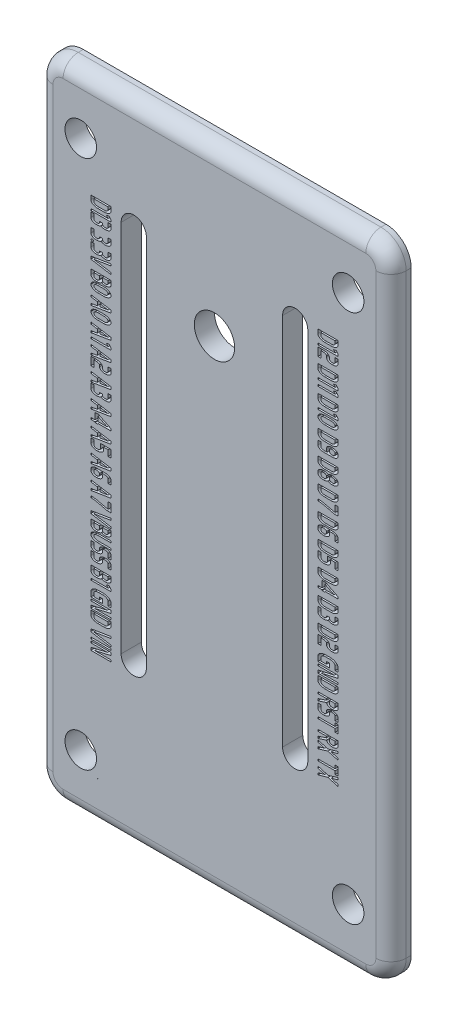
SolidWorks part; units mm, degrees
ref_plane "Front Plane" through (0, 0, 0) normal (0, 0, 1) x (1, 0, 0)
ref_plane "Top Plane" through (0, 0, 0) normal (0, 1, 0) x (1, 0, 0)
ref_plane "Right Plane" through (0, 0, 0) normal (1, 0, 0) x (0, 0, -1)
sketch "Sketch1" plane through (0, 0, 0) normal (0, 0, 1) x (1, 0, 0)
  line L1 (0, 32) -> (0, -32) construction
  line L2 (16.455, 32) -> (-16.455, 32) construction
  line L3 (-16.455, -32) -> (16.455, -32) construction
  line L4 (17.455, 31) -> (17.455, -31) construction
  line L5 (17.455, 0) -> (-17.455, 0) construction
  line L6 (-17.455, 31) -> (-17.455, -31) construction
  line L7 (17.7124, 32) -> (16.455, 32) construction
  line L8 (-15, -32) -> (15, -32)
  line L9 (-17.5, -29.5) -> (-17.5, 29.5)
  line L10 (-15, 32) -> (15, 32)
  line L11 (17.5, -29.5) -> (17.5, 29.5)
  line L12 (0, 32) -> (0, -32) construction
  line L13 (-17.5, 0) -> (17.5, 0) construction
  arc A0 (-15, -32) -> (-17.5, -29.5) centre (-15, -29.5) cw
  arc A1 (15, -32) -> (17.5, -29.5) centre (15, -29.5) ccw
  arc A2 (15, 32) -> (17.5, 29.5) centre (15, 29.5) cw
  arc A3 (-17.5, 29.5) -> (-15, 32) centre (-15, 29.5) cw
  circle A4 centre (-11.5563, -27.8796) radius 0.0197
  circle A5 centre (-13.25, -26.25) radius 1.5625
  circle A6 centre (-13.25, 26.25) radius 1.5625
  circle A7 centre (-13.25, -26.25) radius 2.37 construction
  circle A8 centre (13.25, -26.25) radius 1.5625
  circle A9 centre (13.25, 26.25) radius 1.5625
  point P12 (0, 0)
  point P25 (17.5, 32)
  dimension "D3" = 2.5
  dimension "D4" = 0.0393
  dimension "D5" = 3.125
  dimension "D1" = 35
  dimension "D2" = 64
  dimension "D6" = 11.5563
  dimension "D7" = 27.8796
extrude "Boss-Extrude1" add sketch "Sketch1" along normal blind 2
sketch "Sketch2" plane through (0, 0, 2) normal (0, 0, 1) x (1, 0, 0)
  line L0 (-13.6273, 22.1478) -> (-13.6273, -16.8522) construction
  line L1 (-11.75, 22.1478) -> (-15.5046, 22.1478) construction
  line L2 (-15.5046, -16.8522) -> (-11.75, -16.8522) construction
  line L4 (0, 2.52) -> (-13.6273, 2.52) construction
  line L6 (-8, -16) -> (-8, 21.04) construction
  line L9 (0, -16.85) -> (0, 21.89) construction
  line L12 (-9.25, -16) -> (-9.25, 21.04)
  line L15 (-6.75, -16) -> (-6.75, 21.04)
  line L16 (8, -16) -> (8, 21.04) construction
  line L17 (9.25, -16) -> (9.25, 21.04)
  line L18 (6.75, -16) -> (6.75, 21.04)
  line L19 (17.5, -29.5) -> (17.5, 29.5) construction
  line L20 (-15, -32) -> (15, -32) construction
  line L21 (-13.6273, 2.6478) -> (0, 2.6478) construction
  arc A4 (-9.25, -16) -> (-6.75, -16) centre (-8, -16) ccw
  arc A5 (-6.75, 21.04) -> (-9.25, 21.04) centre (-8, 21.04) ccw
  arc A6 (9.25, -16) -> (6.75, -16) centre (8, -16) cw
  arc A7 (6.75, 21.04) -> (9.25, 21.04) centre (8, 21.04) cw
  point P11 (8, 2.52)
  point P14 (-8, 2.52)
  dimension "D3" = 17.5
  dimension "D4" = 16
  dimension "D2" = 9.5
  dimension "D1" = 2.5
  dimension "D5" = 34.52
fillet "Fillet1" radius 1.5 8 edges at (-16.7678, -31.2678, 2) (0, -32, 2) (16.7678, -31.2678, 2) (16.7678, 31.2678, 2) (17.5, 0, 2) (-16.7678, 31.2678, 2) (-17.5, 0, 2) (0, 32, 2)
sketch "Sketch3" plane through (0, 0, 2) normal (0, 0, 1) x (1, 0, 0)
  line L0 (16, -29.5) -> (16, 29.5) construction
  line L6 (-8.88, 26.4) -> (8.88, 26.4) construction
  circle A0 centre (0, 15.9) radius 2
  dimension "D1" = 10.5
  dimension "D2" = 4
  dimension "D3" = 16
extrude "Cut-Extrude2" cut sketch "Sketch3" against normal through all contours A0
extrude "Cut-Extrude3" cut sketch "Sketch2" against normal through all
sketch "Sketch4" plane through (0, 0, 2) normal (0, 0, 1) x (1, 0, 0)
  line L0 (-12.25, -17.25) -> (-12.25, 22.29) construction
  line L3 (-9.25, 21.04) -> (-9.25, -16) construction
  line L4 (10.25, 22.29) -> (10.25, -17.25) construction
  line L5 (9.25, -16) -> (9.25, 21.04) construction
  text T0 "D13 3.3V B0 A0 A1 A2 A3 A4 A5 A6 A7 VBUSS B1 GND VIN" font "BANSED" height 2
  text T1 "D12 D11 D10 D9 D8 D7 D6 D5 D4 D3 D2 GND RST RX TX" font "BANSED" height 2
  dimension "D1" = 3
  dimension "D2" = 1
  dimension "D3" = 9.25
  dimension "D4" = 13.25
  dimension "D5" = 30.5
  dimension "D6" = 52.79
extrude "Cut-Extrude4" cut sketch "Sketch4" against normal blind 0.75
